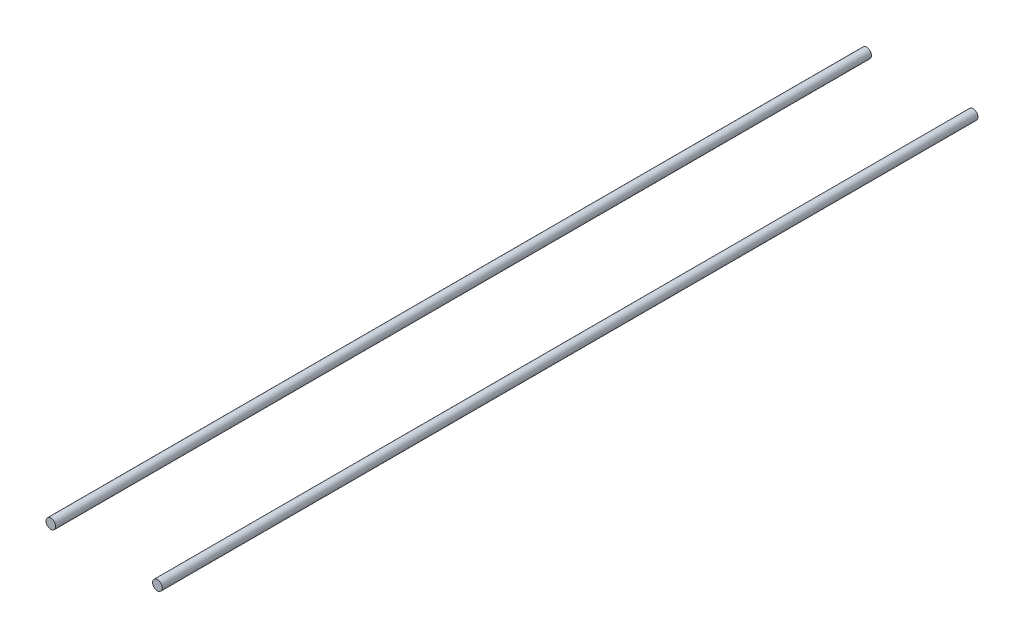
SolidWorks part; units mm, degrees
ref_plane "Front Plane" through (0, 0, 0) normal (0, 0, 1) x (1, 0, 0)
ref_plane "Top Plane" through (0, 0, 0) normal (0, 1, 0) x (1, 0, 0)
ref_plane "Right Plane" through (0, 0, 0) normal (1, 0, 0) x (0, 0, -1)
ref_plane "Plane1" through (0, 0, 200) normal (0, 0, -1) x (-1, 0, 0)
sketch "Sketch1" plane through (0, 0, 200) normal (0, 0, -1) x (-1, 0, 0)
  line L0 (-90.0001, -30.8878) -> (89.9999, -30.8878) construction
  line L1 (0, 70.1122) -> (0, -75.0001) construction
  line L2 (-50.5, -30.8878) -> (50.5, -30.8878) construction
  line L3 (-50.5, -30.8878) -> (-50.5, 70.1122) construction
  line L4 (-50.5, 70.1122) -> (50.5, 70.1122) construction
  line L5 (50.5, -30.8878) -> (50.5, 70.1122) construction
  circle A0 centre (-65.5, -30.8878) radius 6
  circle A2 centre (65.5, -30.8878) radius 6
  spline S0 degree 3 poles (-95, 100.1689) (-95, 99.9993) (-95, 99.9964) (-95, 99.9928) (-95, 99.9874) (-95, 99.9749) (-95, 99.9497) (-95, 99.8995) (-95, 99.799) (-95, 99.598) (-95, 99.196) (-95, 98.392) (-95, 96.784) (-95, 93.5679) (-95, 87.1359) (-95, 81.6227) (-95, 70.5964) (-95, 63.2455) (-95, 41.1927) (-95, 22.8155) (-95, 4.2085) (-95, 0.3033) (-95, -0.0413) (-95, -0.15) (-94.9995, -0.3707) (-94.9976, -0.9224) (-94.9829, -2.3558) (-94.9471, -3.6763) (-94.8447, -6.313) (-94.7351, -8.0652) (-94.2711, -13.2968) (-93.781, -16.7505) (-92.3743, -23.5302) (-91.4572, -26.8546) (-89.7203, -31.6821) (-89.0817, -33.2636) (-87.6794, -36.3621) (-86.9158, -37.8795) (-85.2643, -40.8354) (-84.3762, -42.2733) (-82.4744, -45.0646) (-81.4616, -46.4169) (-78.2486, -50.3244) (-75.8666, -52.7366) (-70.7044, -57.1297) (-67.9222, -59.1147) (-62.0605, -62.6615) (-58.9802, -64.2249) (-52.6088, -66.9709) (-49.3209, -68.1542) (-42.6122, -70.189) (-39.1884, -71.041) (-32.2538, -72.4676) (-28.7476, -73.0417) (-21.6814, -73.9534) (-18.1202, -74.2916) (-10.9713, -74.772) (-7.3829, -74.9132) (-1.9872, -74.9989) (-0.1854, -75.0066) (3.415, -74.9827) (5.2133, -74.9505) (10.6005, -74.7874) (14.1817, -74.5902) (21.3129, -73.9887) (24.8595, -73.5849) (31.8912, -72.5281) (35.3791, -71.8753) (42.2571, -70.2781) (45.6447, -69.3328) (52.266, -67.0957) (55.5033, -65.8035) (61.7404, -62.827) (64.7415, -61.1407) (68.9962, -58.292) (70.3742, -57.2887) (73.0346, -55.1767) (74.316, -54.0684) (76.7745, -51.745) (77.9514, -50.5304) (80.1884, -48.0037) (81.2482, -46.691) (84.2485, -42.6117) (86.0017, -39.7107) (89.0071, -33.6212) (90.2575, -30.4376) (92.2908, -23.8805) (93.0733, -20.5094) (94.2309, -13.6581) (94.6061, -10.1784) (94.9124, -4.9201) (94.9865, -2.7208) (94.9997, -0.5145) (95, 0.0374) (95, 0.1537) (95, 0.3835) (95, 0.728) (95, 1.9915) (95, 17.8419) (95, 33.4625) (95, 62.8662) (95, 79.4057) (95, 96.4047) (95, 98.9315) (95, 99.6494) (95, 99.9222) (95, 99.9689) (95, 99.9868) (95, 99.994) (95, 99.9991) (95, 100.003) (95, 100.0268) (94.9991, 100.0925) (94.9961, 100.1546) (94.9877, 100.2775) (94.9785, 100.3573) (94.954, 100.5109) (94.9391, 100.5827) (94.8816, 100.8069) (94.8258, 100.9667) (94.6797, 101.2883) (94.5845, 101.4611) (94.3455, 101.8226) (94.2016, 102.0114) (93.8582, 102.4054) (93.6595, 102.6093) (93.2238, 103.0127) (92.9849, 103.2141) (92.4673, 103.6145) (92.1876, 103.8143) (91.5989, 104.2064) (91.292, 104.3973) (90.3356, 104.9562) (89.6468, 105.3123) (88.2144, 105.9838) (87.4677, 106.3002) (85.9329, 106.8992) (85.1471, 107.1807) (82.7417, 107.9818) (81.0852, 108.4554) (77.7141, 109.3132) (75.9985, 109.6974) (72.534, 110.3975) (70.7842, 110.7134) (65.502, 111.5804) (61.9373, 112.0522) (54.7681, 112.8552) (51.1631, 113.1855) (43.9313, 113.7435) (40.3036, 113.9709) (33.036, 114.3479) (29.3958, 114.4967) (18.4613, 114.8506) (11.1566, 114.9634) (0.1894, 115.007) (-3.4683, 115.0012) (-10.7775, 114.9459) (-14.4303, 114.8958) (-25.379, 114.6647) (-32.667, 114.4055) (-43.5566, 113.7666) (-47.1781, 113.5116) (-54.395, 112.8882) (-57.9912, 112.5207) (-65.1309, 111.6267) (-68.677, 111.1011) (-73.9138, 110.1299) (-75.6447, 109.7754) (-79.0596, 108.9861) (-80.7447, 108.5514) (-84.0288, 107.5758) (-85.6293, 107.0349) (-87.9085, 106.1152) (-88.6431, 105.7923) (-89.7002, 105.2767) (-90.0453, 105.0996) (-90.7111, 104.7379) (-91.0327, 104.5527) (-91.6515, 104.1727) (-91.9503, 103.9768) (-92.5142, 103.5798) (-92.7778, 103.3797) (-93.2639, 102.9777) (-93.4864, 102.7759) (-93.8894, 102.3722) (-94.0685, 102.1714) (-94.37, 101.7895) (-94.4935, 101.6073) (-94.6953, 101.2591) (-94.7711, 101.0982) (-94.8605, 100.8603) (-94.8858, 100.7823) (-94.9279, 100.6307) (-94.9442, 100.5592) (-94.985, 100.3327) (-95, 100.1689) (-95, 99.9993) (-95, 99.9964) knots -0.001953 -0.001953 0 0 0.000008 0.000008 0.000015 0.000031 0.000061 0.000122 0.000244 0.000488 0.000977 0.001953 0.003906 0.007812 0.015625 0.03125 0.03125 0.0625 0.0625 0.125 0.140625 0.141602 0.141602 0.14209 0.14209 0.142578 0.144531 0.148437 0.148437 0.15625 0.15625 0.171875 0.171875 0.1875 0.1875 0.195312 0.195312 0.203125 0.203125 0.210937 0.210937 0.21875 0.21875 0.234375 0.234375 0.25 0.25 0.265625 0.265625 0.28125 0.28125 0.296875 0.296875 0.3125 0.3125 0.328125 0.328125 0.34375 0.34375 0.351562 0.351562 0.359375 0.359375 0.375 0.375 0.390625 0.390625 0.40625 0.40625 0.421875 0.421875 0.4375 0.4375 0.453125 0.453125 0.460937 0.460937 0.46875 0.46875 0.476562 0.476562 0.484375 0.484375 0.5 0.5 0.515625 0.515625 0.53125 0.53125 0.546875 0.546875 0.554687 0.556641 0.556641 0.557129 0.557129 0.557617 0.558594 0.5625 0.625 0.625 0.6875 0.695312 0.697266 0.698242 0.698364 0.698425 0.698441 0.698441 0.698456 0.698456 0.698486 0.69873 0.699219 0.699219 0.700195 0.700195 0.701172 0.701172 0.703125 0.703125 0.705078 0.705078 0.707031 0.707031 0.708984 0.708984 0.710937 0.710937 0.712891 0.712891 0.714844 0.714844 0.71875 0.71875 0.722656 0.722656 0.726562 0.726562 0.734375 0.734375 0.742187 0.742187 0.75 0.75 0.765625 0.765625 0.78125 0.78125 0.796875 0.796875 0.8125 0.8125 0.84375 0.84375 0.859375 0.859375 0.875 0.875 0.90625 0.90625 0.921875 0.921875 0.9375 0.9375 0.953125 0.953125 0.960937 0.960937 0.96875 0.96875 0.976562 0.976562 0.980469 0.980469 0.982422 0.982422 0.984375 0.984375 0.986328 0.986328 0.988281 0.988281 0.990234 0.990234 0.992187 0.992187 0.994141 0.994141 0.996094 0.996094 0.99707 0.99707 0.998047 0.998047 1 1 1.000008 1.000008 1.000015 only from (-95, 100) to (-95, 100) construction
  point P7 (0, 70.1122)
  dimension "D4" = 12
  dimension "D1" = 180
  dimension "D2" = 101
  dimension "D3" = 101
  dimension "D5" = 15
extrude "Boss-Extrude2" add sketch "Sketch1" along normal blind 100 and the other way blind 903.2
sketch "Sketch2" plane through (0, 0, 1103.2) normal (0, 0, 1) x (1, 0, 0)
  line L0 (-78.3443, 70.1122) -> (-78.3443, 73.2872) construction
  line L1 (-78.3443, 73.2872) -> (78.3443, 73.2872) construction
  line L2 (78.3443, 73.2872) -> (78.3443, 70.1122) construction
  line L3 (78.3443, 70.1122) -> (-78.3443, 70.1122) construction
  line L4 (-78.3443, 70.1122) -> (-78.3443, 73.2872)
  line L5 (-78.3443, 73.2872) -> (78.3443, 73.2872)
  line L6 (78.3443, 73.2872) -> (78.3443, 70.1122)
  line L7 (78.3443, 70.1122) -> (-78.3443, 70.1122)
  point P0 (93.5277, 100.1472)
  point P1 (88.5285, 100.0561)
  dimension "D1" = 5
